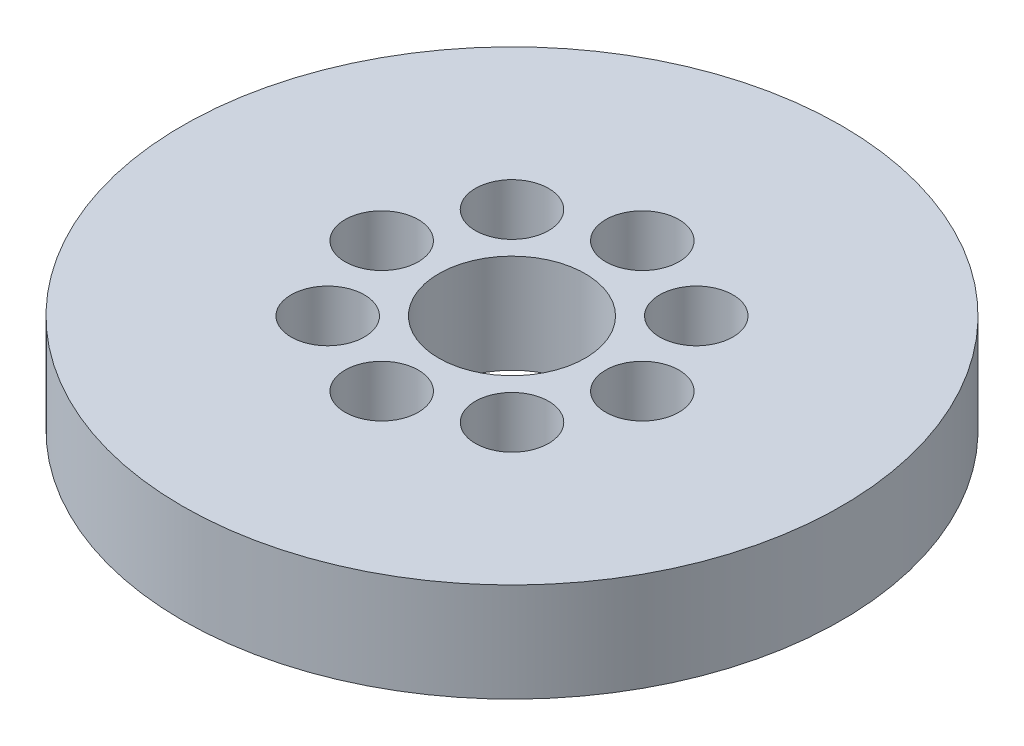
SolidWorks part; units mm, degrees
ref_plane "Front Plane" through (0, 0, 0) normal (0, 0, 1) x (1, 0, 0)
ref_plane "Top Plane" through (0, 0, 0) normal (0, 1, 0) x (1, 0, 0)
ref_plane "Right Plane" through (0, 0, 0) normal (1, 0, 0) x (0, 0, -1)
sketch "Sketch1" plane through (0, 0, 0) normal (0, 1, 0) x (1, 0, 0)
  circle A0 centre (0, 0) radius 90
  dimension "FLANGE_OD" = 180
extrude "Boss-Extrude1" add sketch "Sketch1" along normal blind 27
sketch "Sketch2" plane through (0, 0, 0) normal (0, 1, 0) x (1, 0, 0)
  circle A0 centre (0, 0) radius 20
  dimension "BORE_D" = 40
extrude "Cut-Extrude1" cut sketch "Sketch2" along normal through all
sketch "Sketch3" plane through (0, 27, 0) normal (0, 1, 0) x (1, 0, 0)
  circle A0 centre (0, 0) radius 35.5877 construction
  circle A1 centre (-35.5877, 0) radius 10
  dimension "BOLT_D" = 20
  dimension "BOLT_PCD" = 71.1754
extrude "Cut-Extrude2" cut sketch "Sketch3" against normal blind 20.2621
pattern_circular "CirPattern1" count 8 over 360 about axis through (0, 0, 0) along (0, 1, 0) of "Cut-Extrude2"
